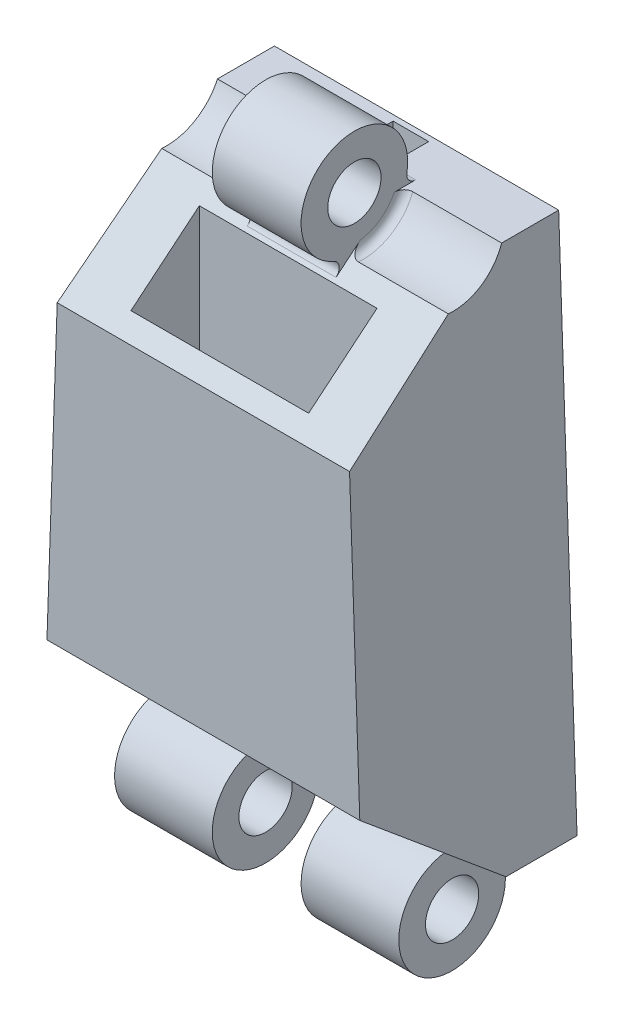
SolidWorks part; units mm, degrees
ref_plane "Front Plane" through (0, 0, 0) normal (0, 0, 1) x (1, 0, 0)
ref_plane "Top Plane" through (0, 0, 0) normal (0, 1, 0) x (1, 0, 0)
ref_plane "Right Plane" through (0, 0, 0) normal (1, 0, 0) x (0, 0, -1)
sketch "Sketch1" plane through (0, 0, 0) normal (0, 0, 1) x (1, 0, 0)
  line L0 (-8, -14.5) -> (-6.9661, 15.4822)
  line L3 (-8, -14.5) -> (10.0677, -14.5)
  line L5 (10.0677, -14.5) -> (9.0339, 15.4822)
  line L6 (-6.9661, 15.4822) -> (9.0339, 15.4822)
  point P0 (0, 0)
extrude "Boss-Extrude2" add sketch "Sketch1" along normal blind 12
sketch "Sketch15" plane through (0, 0, 0) normal (0, 0, -1) x (-1, 0, 0)
  line L0 (6.9661, 15.4822) -> (-9.0339, 15.4822)
  line L1 (-1.0339, 15.4822) -> (-1.0339, 5.488)
ref_plane "Plane1" through (1.0339, 0, 0) normal (1, 0, 0) x (0, 0, -1)
sketch "Sketch16" plane through (1.0339, 0, 0) normal (1, 0, 0) x (0, 0, -1)
  line L0 (0, 15.4822) -> (-4, 15.4822)
  line L6 (-12, 15.4822) -> (0, 15.4822) construction
  line L7 (-4, 15.4822) -> (-12, 8.8525)
  line L8 (-12, -14.5) -> (-12, 15.4822) construction
  line L9 (-12, 8.8525) -> (-12, 15.4822)
  line L10 (-12, 15.4822) -> (-4, 15.4822)
extrude "Cut-Extrude2" cut sketch "Sketch16" against normal through all both and the other way through all contours L10 L9 L7 region at (1.0339, 13.2723, 9.3333)
sketch "Sketch17" plane through (1.0339, 0, 0) normal (1, 0, 0) x (0, 0, -1)
  line L0 (-12, 8.8525) -> (-12, 18.723)
  line L1 (0, 15.4822) -> (-12, 15.4822)
  line L2 (-6, 15.4822) -> (-6, 16.5822)
  circle A0 centre (-6, 16.5822) radius 1.5
  circle A1 centre (-6, 16.5822) radius 3
extrude "Boss-Extrude3" add sketch "Sketch17" along normal mid plane 5 contours L1 A1 A0 | L1 A1 A0 region at (1.0339, 14.6478, 6) region at (1.0339, 15.5549, 4.0946)
sketch "Sketch18" plane through (1.0339, 0, 0) normal (1, 0, 0) x (0, 0, -1)
  line L0 (0, -14.5) -> (-4, -14.5)
  line L1 (-12, -14.5) -> (0, -14.5) construction
  line L2 (-4, -14.5) -> (-12, -7.8704)
  line L3 (-12, -14.5) -> (-12, 8.8525) construction
  line L4 (-12, -7.8704) -> (-12, -14.5)
  line L5 (-12, -14.5) -> (-4, -14.5)
extrude "Cut-Extrude3" cut sketch "Sketch18" against normal through all both and the other way through all contours L4 L5 L2 region at (1.0339, -12.2901, 9.3333)
sketch "Sketch19" plane through (1.0339, 0, 0) normal (1, 0, 0) x (0, 0, -1)
  line L0 (-12, -7.8704) -> (-12, -19.6668)
  line L1 (0, -14.5) -> (-3.2089, -14.5)
  line L3 (-8.7911, -14.5) -> (-12, -14.5)
  circle A0 centre (-6, -15.6) radius 1.5
  circle A1 centre (-6, -15.6) radius 3
extrude "Boss-Extrude4" add sketch "Sketch19" along normal mid plane 16 contours A1 A0 region at (1.0339, -18.4639, 6.544)
extrude "Cut-Extrude4" cut sketch "Sketch19<3>" against normal mid plane 5 contours A1
sketch "Sketch19<3>" plane through (1.0339, 0, 0) normal (1, 0, 0) x (0, 0, -1) same geometry as "Sketch19"
sketch "Sketch20" plane through (3.5339, 0, 0) normal (1, 0, 0) x (0, 0, -1)
  circle A0 centre (-6, 16.5822) radius 3
extrude "Cut-Extrude5" cut sketch "Sketch20" along normal blind 10
sketch "Sketch21" plane through (-1.4661, 0, 0) normal (-1, 0, 0) x (0, 0, 1)
  circle A0 centre (6, 16.5822) radius 3
extrude "Cut-Extrude6" cut sketch "Sketch21" along normal blind 10
fillet "Fillet6" radius 0.5 1 edges at (1.0339, 13.595, 6.2772)
fillet "Fillet7" radius 0.5 1 edges at (1.0339, 15.4822, 3.2089)
fillet "Fillet8" radius 0.5 2 edges at (3.5339, 14.0268, 4.4283) (-1.4661, 14.0268, 4.4283)
sketch "Sketch23" plane through (0, 11.1439, 9.235) normal (0, 0.77, 0.6381) x (1, 0, 0)
  line L0 (1.0339, -3.591) -> (1.0339, -2.391)
  line L1 (-7.1947, -3.591) -> (9.2625, -3.591) construction
  line L2 (-3.9661, -2.391) -> (6.0339, -2.391)
  line L3 (6.0339, -2.391) -> (6.0339, 2.609)
  line L4 (6.0339, 2.609) -> (-3.9661, 2.609)
  line L5 (-3.9661, 2.609) -> (-3.9661, -2.391)
  point P7 (1.0339, -2.391)
sketch "Sketch24" plane through (0, 0, 0) normal (0, 1, 0) x (1, 0, 0)
  line L0 (-3.9661, -7.2262) -> (-3.9661, -11.076)
  line L1 (-3.9661, -11.076) -> (6.0339, -11.076)
  line L2 (6.0339, -11.076) -> (6.0339, -7.2262)
  line L3 (6.0339, -7.2262) -> (-3.9661, -7.2262)
extrude "Cut-Extrude7" cut sketch "Sketch24" against normal up to surface and the other way up to surface up to face at (1.0339, -12.4192, 6.5109) other way up to face at (1.0451, 12.5917, 7.4879)
sketch "Sketch25" plane through (1.0339, 0, 0) normal (1, 0, 0) x (0, 0, -1)
  line L0 (-0.32, -14.5) -> (-0.32, -14.3817)
  line L1 (-4, -14.5) -> (0, -14.5) construction
  line L2 (-2.32, -14.5) -> (-2.32, -14.3817)
  line L4 (-0.32, -14.3817) -> (-0.32, 15.8832)
  line L5 (-0.32, 15.8832) -> (-2.32, 15.8832)
  line L6 (-2.32, 15.8832) -> (-2.32, -14.5)
  line L8 (-0.32, -14.5) -> (-2.32, -14.5)
  line L9 (-0.32, -14.5) -> (-2.32, -14.5)
extrude "Cut-Extrude8" cut sketch "Sketch25" against normal mid plane 2 contours L8 L0 L4 L5 L6 L2 region at (1.0339, 0.6916, 1.32)
